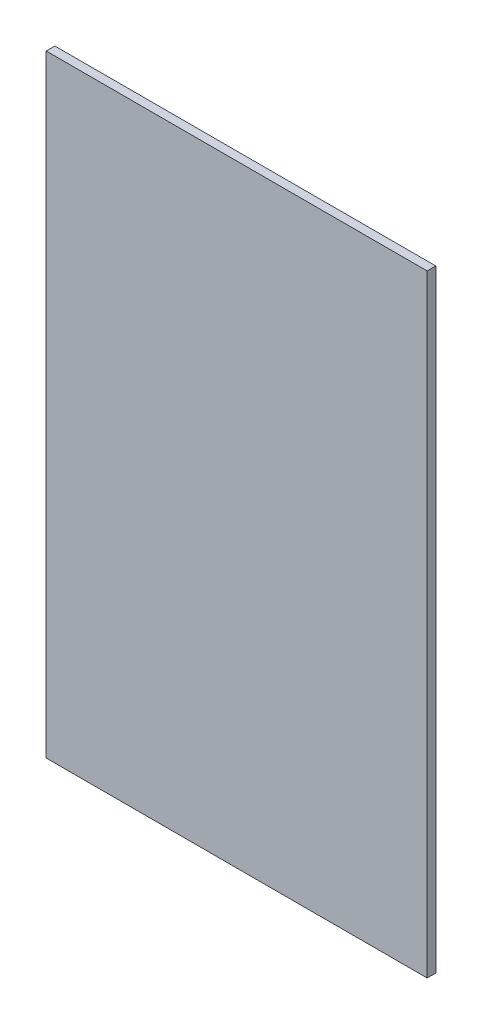
SolidWorks part; units mm, degrees
ref_plane "Front Plane" through (0, 0, 0) normal (1, 0, 0) x (0, 1, 0)
ref_plane "Top Plane" through (0, 0, 0) normal (0, 0, 1) x (0, 1, 0)
ref_plane "Right Plane" through (0, 0, 0) normal (0, 1, 0) x (-1, 0, 0)
sketch "Sketch1" plane through (0, 0, 0) normal (0, 0, 1) x (0, 1, 0)
  line L1 (-112.268, -69.85) -> (112.268, -69.85)
  line L2 (-112.268, -69.85) -> (-112.268, 69.85)
  line L3 (-112.268, 69.85) -> (112.268, 69.85)
  line L4 (112.268, -69.85) -> (112.268, 69.85)
  line L5 (-112.268, -69.85) -> (112.268, 69.85) construction
  line L6 (-112.268, 69.85) -> (112.268, -69.85) construction
  point P1 (0, 0)
  dimension "D1" = 224.536
  dimension "D2" = 139.7
extrude "Boss-Extrude1" add sketch "Sketch1" along normal blind 3.175
